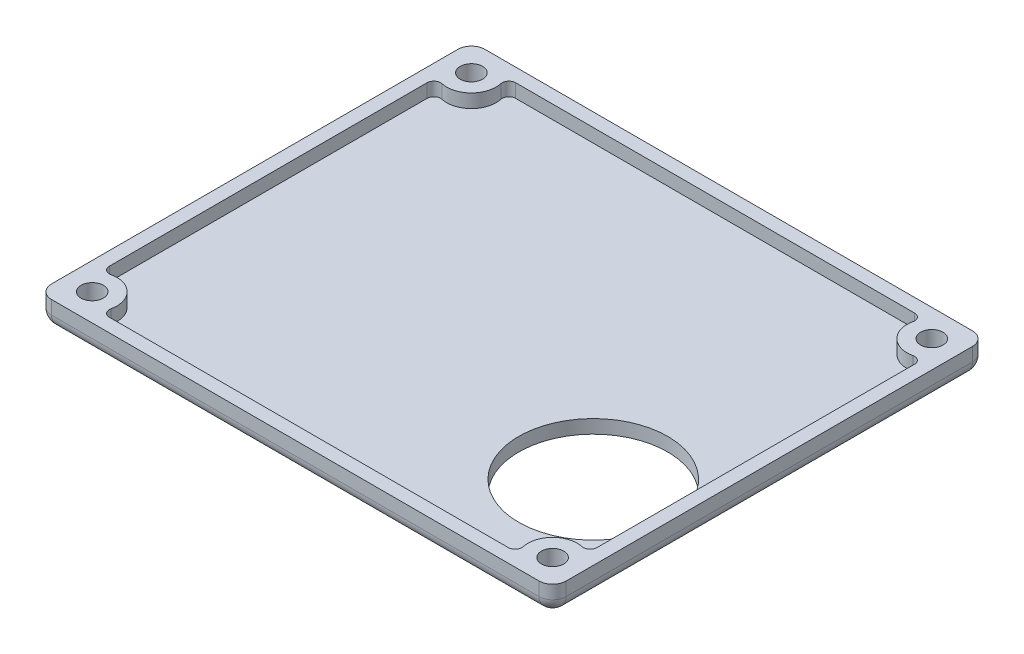
SolidWorks part; units mm, degrees
note: The reader was unsure of these and kept them because the rebuilt part matched: shared geometry of "Schizzo3<11>".
ref_plane "Piano frontale" through (0, 0, 0) normal (0, 0, 1) x (1, 0, 0)
ref_plane "Piano superiore" through (0, 0, 0) normal (0, 1, 0) x (1, 0, 0)
ref_plane "Piano destro" through (0, 0, 0) normal (1, 0, 0) x (0, 0, -1)
sketch "Schizzo1" plane through (0, 0, 0) normal (0, 1, 0) x (1, 0, 0)
  line L1 (-38, 32) -> (38, 32)
  line L2 (-38, 32) -> (-38, -32)
  line L3 (-38, -32) -> (38, -32)
  line L4 (38, 32) -> (38, -32)
  line L5 (-38, 32) -> (38, -32) construction
  line L6 (-38, -32) -> (38, 32) construction
  point P0 (0, 0)
  dimension "D1" = 76
  dimension "D2" = 64
extrude "Estrusione-Estrusione1" add sketch "Schizzo1" along normal blind 4
sketch "Schizzo2" plane through (0, 4, 0) normal (0, 1, 0) x (1, 0, 0)
  line L0 (38, 32) -> (-38, 32) construction
  line L1 (-36, 30) -> (36, 30)
  line L2 (-36, 30) -> (-36, -30)
  line L3 (-36, -30) -> (36, -30)
  line L4 (36, 30) -> (36, -30)
  line L5 (-36, 30) -> (36, -30) construction
  line L6 (-36, -30) -> (36, 30) construction
  line L7 (38, -32) -> (38, 32) construction
  point P0 (0, 0)
  dimension "D1" = 2
  dimension "D2" = 2
extrude "Taglio-Estrusione1" cut sketch "Schizzo2" against normal offset from surface (2 mm away) 2 up to face at (0, 0, 0)
sketch "Schizzo3" plane through (0, 2, 0) normal (0, 1, 0) x (1, 0, 0)
  line L0 (-36, 30) -> (-36, 24.9467)
  line L1 (36, 30) -> (36, 24.9467)
  line L2 (0, 42.9417) -> (0, -43.5578) construction
  line L3 (46.4844, 0) -> (-110.297, 0) construction
  line L10 (38, -32) -> (38, 32) construction
  line L11 (36, 24.9467) -> (36, 30)
  line L12 (36, 30) -> (30.9467, 30)
  line L13 (38, 32) -> (-38, 32) construction
  line L14 (36, 30) -> (30.9467, 30)
  line L15 (-36, 30) -> (-30.9467, 30)
  line L16 (36, -30) -> (36, -24.9467)
  line L17 (36, -30) -> (30.9467, -30)
  line L18 (-36, -30) -> (-30.9467, -30)
  line L19 (-36, -30) -> (-36, -24.9467)
  circle A8 centre (34, 28) radius 1.65
  circle A9 centre (34, 28) radius 3.65
  circle A10 centre (-34, 28) radius 3.65
  circle A13 centre (-34, 28) radius 1.65
  circle A18 centre (34, -28) radius 1.65
  circle A19 centre (34, -28) radius 3.65
  circle A20 centre (-34, -28) radius 1.65
  circle A21 centre (-34, -28) radius 3.65
  dimension "D2" = 3.3
  dimension "D4" = 2
  dimension "D1" = 4
  dimension "D3" = 4
extrude "Estrusione-Estrusione2" add sketch "Schizzo3" along normal up to surface (2 mm away) up to face at (0, 4, 0)
extrude "Taglio-Estrusione4" cut sketch "Schizzo3<11>" against normal through all contours A13 | A20 | A18 | A8
sketch "Schizzo3<11>" plane through (0, 2, 0) normal (0, 1, 0) x (1, 0, 0) same geometry as "Schizzo3"
sketch "Schizzo5" plane through (0, 0, 0) normal (0, -1, 0) x (1, 0, 0)
  line L0 (-38, 32) -> (38, 32) construction
  line L1 (38, 32) -> (38, -32) construction
  circle A0 centre (25, 13) radius 11
  dimension "D1" = 22
  dimension "D2" = 19
  dimension "D3" = 13
extrude "Taglio-Estrusione5" cut sketch "Schizzo5" against normal up to surface (2 mm away) up to face at (0, 2, 0)
fillet "Raccordo1" radius 1 8 edges at (-30.9467, 3, 30) (-36, 3, 24.9467) (-36, 3, -24.9467) (-30.9467, 3, -30) (30.9467, 3, -30) (36, 3, -24.9467) (36, 3, 24.9467) (30.9467, 3, 30)
fillet "Raccordo2" radius 2 8 edges at (0, 0, 32) (38, 0, 0) (0, 0, -32) (-38, 0, 0) (-38, 2, 32) (38, 2, 32) (38, 2, -32) (-38, 2, -32)
